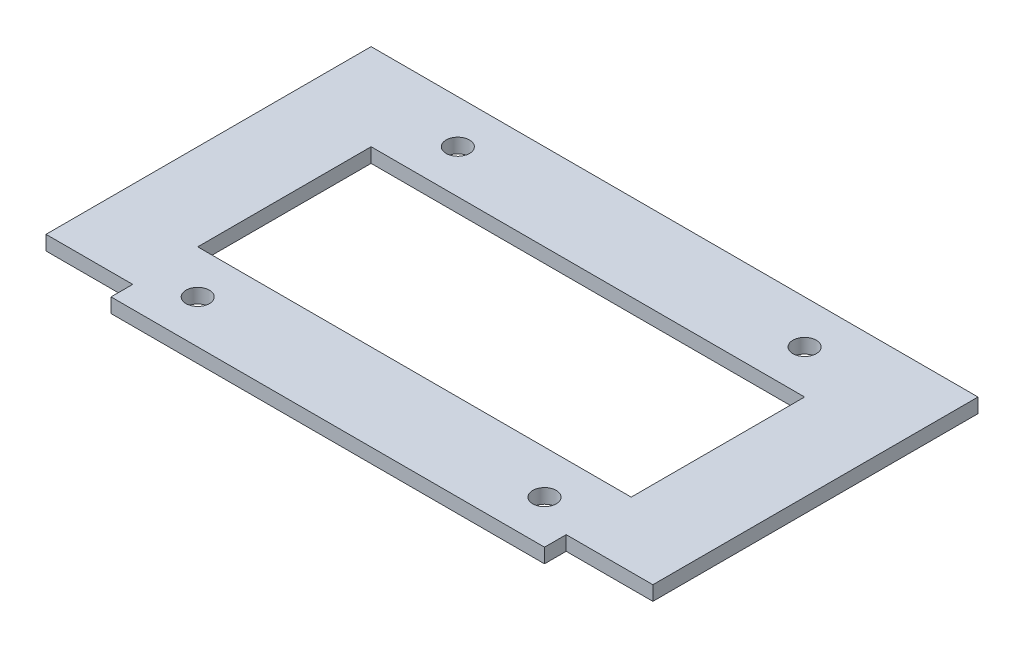
SolidWorks part; units mm, degrees
ref_plane "Front Plane" through (0, 0, 0) normal (0, 0, 1) x (1, 0, 0)
ref_plane "Top Plane" through (0, 0, 0) normal (0, 1, 0) x (1, 0, 0)
ref_plane "Right Plane" through (0, 0, 0) normal (1, 0, 0) x (0, 0, -1)
sketch "Sketch1" plane through (0, 0, 0) normal (0, 1, 0) x (1, 0, 0)
  line L1 (-59.5002, 46.8644) -> (473.8998, 46.8644)
  line L2 (-59.5002, 46.8644) -> (-59.5002, -257.9356)
  line L3 (-59.5002, -257.9356) -> (473.8998, -257.9356)
  line L4 (473.8998, 46.8644) -> (473.8998, -257.9356)
  dimension "D1" = 533.4
  dimension "D2" = 304.8
extrude "Boss-Extrude1" add sketch "Sketch1" along normal blind 12.7
sketch "Sketch2" plane through (0, 12.7, 0) normal (0, 1, 0) x (1, 0, 0)
  line L0 (-59.5002, -238.8856) -> (473.8998, -238.8856) construction
  line L1 (-59.5002, 46.8644) -> (-59.5002, -257.9356) construction
  line L2 (473.8998, -257.9356) -> (473.8998, 46.8644) construction
  line L3 (-59.5002, -257.9356) -> (473.8998, -257.9356) construction
  line L6 (16.6998, -181.7356) -> (397.6998, -181.7356)
  line L7 (16.6998, -181.7356) -> (16.6998, -29.3356)
  line L8 (16.6998, -29.3356) -> (397.6998, -29.3356)
  line L9 (397.6998, -181.7356) -> (397.6998, -29.3356)
  line L10 (473.8998, -29.3356) -> (397.6998, -29.3356) construction
  line L11 (397.6998, -29.3356) -> (397.6998, -181.7356) construction
  line L12 (397.6998, -181.7356) -> (16.6998, -181.7356) construction
  line L13 (16.6998, -181.7356) -> (16.6998, -29.3356) construction
  line L14 (473.8998, -257.9356) -> (397.6998, -257.9356)
  line L15 (473.8998, -257.9356) -> (473.8998, -238.8856)
  line L16 (473.8998, -238.8856) -> (397.6998, -238.8856)
  line L17 (397.6998, -257.9356) -> (397.6998, -238.8856)
  line L18 (-59.5002, -257.9356) -> (16.6998, -257.9356)
  line L19 (-59.5002, -257.9356) -> (-59.5002, -238.8856)
  line L20 (-59.5002, -238.8856) -> (16.6998, -238.8856)
  line L21 (16.6998, -257.9356) -> (16.6998, -238.8856)
  dimension "D1" = 19.05
  dimension "D2" = 19.05
  dimension "D3" = 19.05
  dimension "D4" = 76.2
  dimension "D5" = 76.2
extrude "Cut-Extrude1" cut sketch "Sketch2" against normal blind 12.7
sketch "Sketch4" plane through (0, 12.7, 0) normal (0, 1, 0) x (1, 0, 0)
  line L0 (16.6998, -257.9356) -> (16.6998, -238.8856) construction
  line L1 (16.6998, -181.7356) -> (397.6998, -181.7356) construction
  line L2 (397.6998, -238.8856) -> (397.6998, -257.9356) construction
  line L3 (397.6998, -181.7356) -> (397.6998, -29.3356) construction
  line L4 (397.6998, -29.3356) -> (16.6998, -29.3356) construction
  line L5 (16.6998, -29.3356) -> (16.6998, -181.7356) construction
  circle A0 centre (54.7998, 8.7644) radius 10.287
  circle A1 centre (359.5998, 8.7644) radius 10.287
  circle A2 centre (54.7998, -219.8356) radius 10.287
  circle A3 centre (359.5998, -219.8356) radius 10.287
  dimension "D1" = 20.574
  dimension "D2" = 20.574
  dimension "D3" = 20.574
  dimension "D4" = 20.574
  dimension "D7" = 38.1
  dimension "D9" = 38.1
  dimension "D10" = 38.1
  dimension "D11" = 38.1
  dimension "D5" = 38.1
  dimension "D6" = 38.1
  dimension "D8" = 38.1
  dimension "D12" = 38.1
extrude "Cut-Extrude2" cut sketch "Sketch4" against normal blind 12.7
